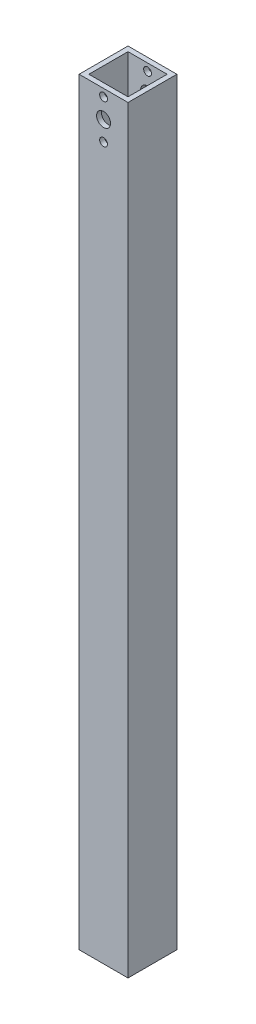
SolidWorks part; units mm, degrees
ref_plane "Plano frontal" through (0, 0, 0) normal (0, 0, 1) x (1, 0, 0)
ref_plane "Plano superior" through (0, 0, 0) normal (0, 1, 0) x (1, 0, 0)
ref_plane "Plano direito" through (0, 0, 0) normal (1, 0, 0) x (0, 0, -1)
sketch "Esboço1" plane through (0, 0, 0) normal (0, 1, 0) x (1, 0, 0)
  line L1 (0, 0) -> (20, 0)
  line L2 (0, 0) -> (0, 20)
  line L3 (0, 20) -> (20, 20)
  line L4 (20, 0) -> (20, 20)
  dimension "D1" = 20
extrude "Extrusão-Fina1" add sketch "Esboço1" along normal blind 310 thin thin type one direction reverse wall 2
sketch "Esboço4" plane through (0, 0, 0) normal (0, 0, 1) x (1, 0, 0)
  line L0 (10, 307) -> (10, 291) construction
  line L1 (0, 310) -> (20, 310) construction
  circle A0 centre (10, 299) radius 2.85
  circle A1 centre (10, 291) radius 1.6
  circle A2 centre (10, 307) radius 1.6
  circle A3 centre (10, 299) radius 11 construction
  point P8 (10, 310)
  dimension "D1" = 3.2
  dimension "D2" = 5.7
  dimension "D4" = 22
  dimension "D3" = 16
extrude "Corte-extrusão2" cut sketch "Esboço4" against normal through all
